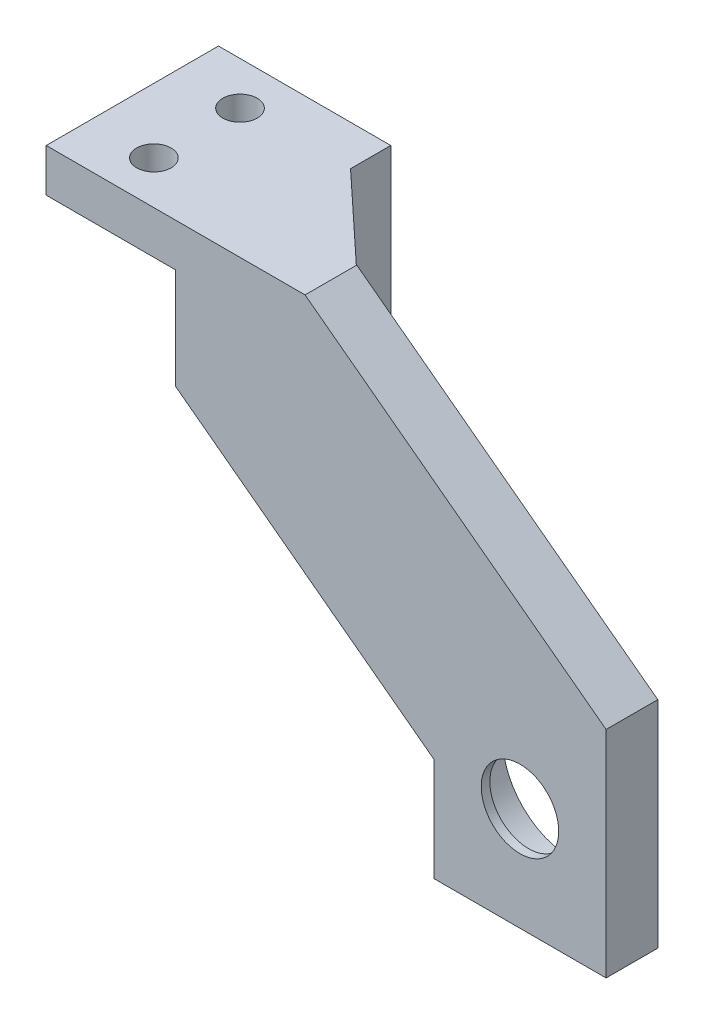
SolidWorks part; units mm, degrees
ref_plane "Front Plane" through (0, 0, 0) normal (0, 0, 1) x (1, 0, 0)
ref_plane "Top Plane" through (0, 0, 0) normal (0, 1, 0) x (1, 0, 0)
ref_plane "Right Plane" through (0, 0, 0) normal (1, 0, 0) x (0, 0, -1)
sketch "Sketch1" plane through (0, 0, 0) normal (0, 0, 1) x (1, 0, 0)
  circle A0 centre (0, 0) radius 4.5
  circle A1 centre (0, 0) radius 8
  circle A2 centre (0, 0) radius 10
  circle A3 centre (0, 0) radius 8 construction
  dimension "D1" = 9
  dimension "D2" = 20
extrude "Boss-Extrude1" add sketch "Sketch1" along normal blind 1 contours A2 A1 | A1 A0 region at (-7.7737, 0, 0) region at (-9.7172, 0, 0)
extrude "Boss-Extrude2" add sketch "Sketch1<4>" against normal up to surface (5 mm away) contours A2 A1 region at (-9.7172, 0, 0)
sketch "Sketch1<4>" plane through (0, 0, 0) normal (0, 0, 1) x (1, 0, 0) same geometry as "Sketch1"
sketch "Sketch2" plane through (0, 0, 1) normal (0, 0, 1) x (1, 0, 0)
  line L0 (-40, 22.5) -> (-10, 0)
  line L1 (-10, 0) -> (-10, -12)
  line L2 (-10, -12) -> (-10, 0) construction
  line L3 (-10, -12) -> (10, -12)
  line L4 (10, -12) -> (10, 34.2)
  line L5 (110, 34.2) -> (-290, 34.2) construction
  line L6 (10, 39.2) -> (10, -12) construction
  line L7 (10, 34.2) -> (-40, 34.2)
  line L8 (-40, 34.2) -> (-40, 22.5)
  circle A0 centre (0, 0) radius 10 construction
  circle A1 centre (0, 0) radius 10
  circle M1 centre (0, 0) radius 10
extrude "Boss-Extrude3" add sketch "Sketch2" against normal up to surface (6 mm away) contours L7 L8 L0 L4 M1 | L3 L4 L1 M1 region at (-12.7734, 21.4272, 1) region at (0, -10.2332, 1) up to face at (10, 0, -5)
sketch "Sketch3" plane through (0, 34.2, 0) normal (0, 1, 0) x (1, 0, 0)
  line L0 (-40, -1) -> (-55, -1)
  line L1 (-55, -1) -> (-55, 19)
  line L2 (-55, 19) -> (-40, 19)
  line L3 (-40, -31) -> (-40, 269) construction
  line L4 (-40, 19) -> (-40, 5)
  line L5 (-55, 236) -> (-55, 256) construction
  line L6 (-40, 19) -> (-35, 19)
  line L7 (-35, 19) -> (-35, 5)
  line L8 (-40, 5) -> (10, 5) construction
  line L9 (-35, 14.33) -> (-25, 5)
  line L11 (-35, 236) -> (-35, 240.6667) construction
  line L13 (-40, 5) -> (10, 5)
  line L14 (-40, 5) -> (-40, -1)
  line L15 (-40, -1) -> (10, -1)
  line L16 (10, 5) -> (10, -1)
  line L17 (-40, 5) -> (10, -1) construction
  line L18 (-40, -1) -> (10, 5) construction
  point P21 (-15, 2)
  line M32 (-40, -31) -> (-40, 269)
  dimension "D1" = 0
  dimension "D2" = 4.67
  dimension "D3" = 0
extrude "Boss-Extrude4" add sketch "Sketch3" along normal up to surface (5 mm away) contours L2 L1 L0 M32 | L13 L7 L6 M32 | L7 L13 L9 | L16 L13 L15 M32 region at (-47.5, 34.2, -9) region at (-15, 34.2, -2) region at (-37.5, 34.2, -12) region at (-31.6667, 34.2, -8.11)
extrude "Boss-Extrude5" add sketch "Sketch3<4>" against normal up to surface (11.7 mm away) contours L13 L7 L6 M32 | L7 L13 L9 region at (-37.5, 34.2, -12) region at (-31.6667, 34.2, -8.11) up to face at (-25, 11.25, -2)
sketch "Sketch3<4>" plane through (0, 34.2, 0) normal (0, 1, 0) x (1, 0, 0) same geometry as "Sketch3"
sketch "Sketch4" plane through (0, 39.2, 0) normal (0, 1, 0) x (1, 0, 0)
  line L0 (-55, -1) -> (10, -1) construction
  line L1 (-55, 19) -> (-40, 19) construction
  line L2 (-55, 19) -> (-55, -1) construction
  line L3 (-55, -1) -> (-40, -1) construction
  line L4 (-40, 19) -> (-40, -1) construction
  line L5 (-55, 19) -> (-40, -1) construction
  line L6 (-55, -1) -> (-40, 19) construction
  line L8 (-40, -31) -> (-40, 269) construction
  line L9 (-55, 9) -> (-40, 9) construction
  circle A0 centre (-47.5, 14) radius 2
  circle A1 centre (-47.5, 14) radius 4 construction
  circle A3 centre (-47.5, 4) radius 4 construction
  circle A4 centre (-47.5, 4) radius 2
  point P4 (-47.5, 9)
  dimension "D1" = 4
  dimension "D2" = 8
  dimension "D3" = 5
  dimension "D4" = 7.5
extrude "Cut-Extrude1" cut sketch "Sketch4" against normal through all
sketch "Sketch5" plane through (0, 0, 1) normal (0, 0, 1) x (1, 0, 0)
  line L0 (0, 20.4884) -> (-24.9488, 39.2)
  line L2 (-40, 22.5) -> (-10, 0) construction
  line L3 (-55, 39.2) -> (10, 39.2) construction
  line L4 (0, 20.4884) -> (10, 12.9884)
  line L6 (10, -12) -> (10, 39.2) construction
  line L7 (-24.9488, 39.2) -> (10, 39.2)
  line L8 (10, 39.2) -> (10, 12.9884)
  dimension "D1" = 20.4884
  dimension "D2" = 0
extrude "Cut-Extrude2" cut sketch "Sketch5" against normal through all both and the other way through all
